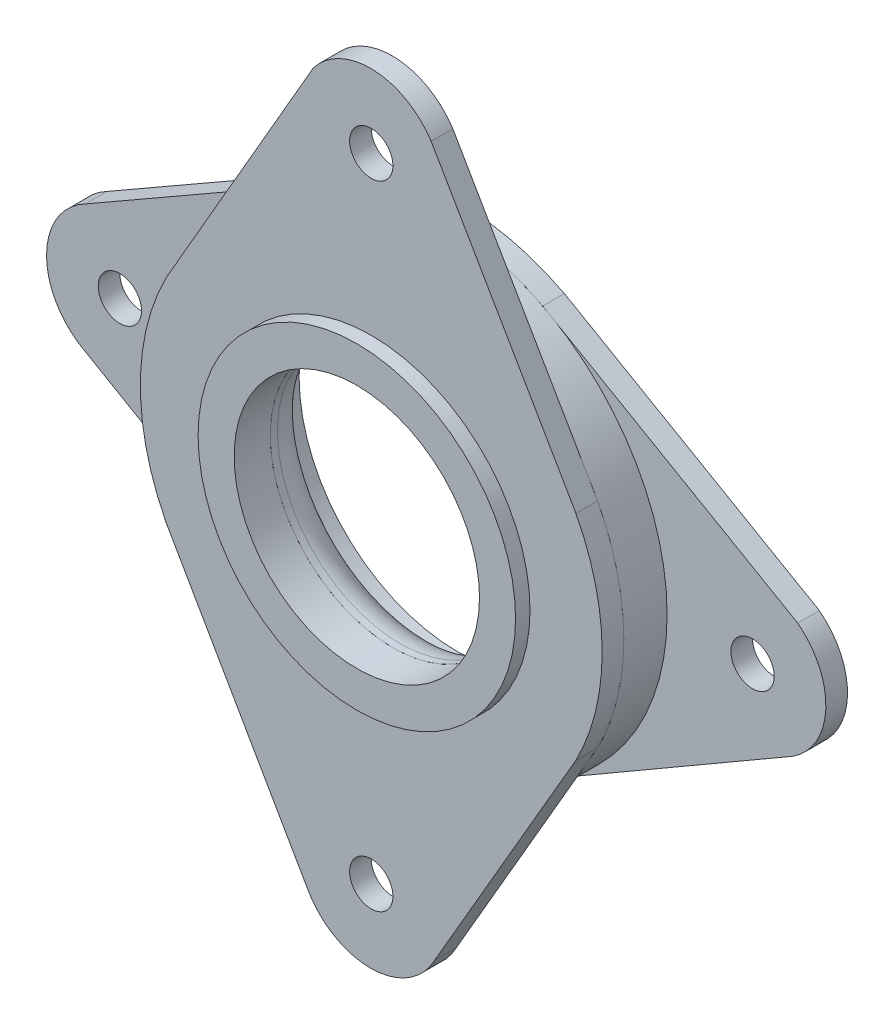
SolidWorks part; units mm, degrees
ref_plane "Front Plane" through (0, 0, 0) normal (0, 0, 1) x (1, 0, 0)
ref_plane "Top Plane" through (0, 0, 0) normal (0, 1, 0) x (1, 0, 0)
ref_plane "Right Plane" through (0, 0, 0) normal (1, 0, 0) x (0, 0, -1)
sketch "Sketch1" plane through (0, 0, 0) normal (0, 0, 1) x (1, 0, 0)
  line L1 (7.3794, 14.1966) -> (25.0466, 4.0094)
  line L2 (-24.3098, 4.4793) -> (-7.325, 14.2248)
  line L3 (-24.3029, -4.3932) -> (-7.4267, -14.1719)
  line L4 (7.408, -14.1817) -> (24.7169, -4.1525)
  line L7 (20.4006, 0) -> (41.1933, 0) construction
  arc A0 (-7.4267, -14.1719) -> (7.408, -14.1817) centre (0, 0) ccw construction
  circle A1 centre (0, 0) radius 27 construction
  arc A4 (24.7169, -4.1525) -> (25.0466, 4.0094) centre (22, 0.0449) ccw
  arc A5 (-7.4267, -14.1719) -> (7.408, -14.1817) centre (0, 0) ccw
  arc A6 (-24.3098, 4.4793) -> (-24.3029, -4.3932) centre (-22, 0.0449) ccw
  arc A7 (7.3794, 14.1966) -> (-7.325, 14.2248) centre (0, 0) ccw construction
  arc A8 (7.3794, 14.1966) -> (-7.325, 14.2248) centre (0, 0) ccw
  point P7 (0, 0)
  dimension "D1" = 32
  dimension "D2" = 54
  dimension "D7" = 10
  dimension "D6" = 22
extrude "Boss-Extrude1" add sketch "Sketch1" along normal blind 1.5
sketch "Sketch2" plane through (0, 0, 1.5) normal (0, 0, 1) x (1, 0, 0)
  line L0 (31.1876, 0) -> (-31.1876, 0) construction
  circle A0 centre (-21.92, 0) radius 1.5
  circle A1 centre (21.92, 0) radius 1.5
  circle A2 centre (0, 0) radius 8.5
  point P9 (0, 0)
  dimension "D1" = 17
  dimension "D2" = 3
  dimension "D3" = 3
  dimension "D4" = 21.92
  dimension "D5" = 21.92
extrude "Cut-Extrude1" cut sketch "Sketch2" against normal through all
ref_plane "Plane1" through (0, 0, 3) normal (0, 0, 1) x (1, 0, 0)
mirror "Mirror2" about plane through (0, 0, 3) normal (0, 0, 1) of bodies 102
move or copy body "Body-Move/Copy1" bodies to move or copy 104 copy no rotation origin (0, 0, 0) rotation axis (0, 0, 1) rotation angle 90
sketch "Sketch3" plane through (0, 0, 3) normal (0, 0, 1) x (1, 0, 0)
  circle A0 centre (0, 0) radius 16
  circle A1 centre (0, 0) radius 8.5
  dimension "D1" = 32
extrude "Boss-Extrude2" add sketch "Sketch3" along normal blind 1.5 and the other way blind 1.5 separate body
sketch "Sketch4" plane through (0, 0, 0) normal (0, 0, -1) x (-1, 0, 0)
  circle A0 centre (0, 0) radius 11
  dimension "D1" = 22
extrude "Cut-Extrude2" cut sketch "Sketch4" against normal up to surface (1.5 mm away) up to face at (-20.42, 0, 1.5)
fillet "Fillet1" radius 2.5 1 edges at (8.5, 0, 1.5)
sketch "Sketch6" plane through (0, 0, 6) normal (0, 0, 1) x (1, 0, 0)
  circle A0 centre (0, 0) radius 8.5
  circle A1 centre (0, 0) radius 11
  dimension "D1" = 22
  dimension "D2" = 17
extrude "Boss-Extrude4" add sketch "Sketch6" along normal blind 1
